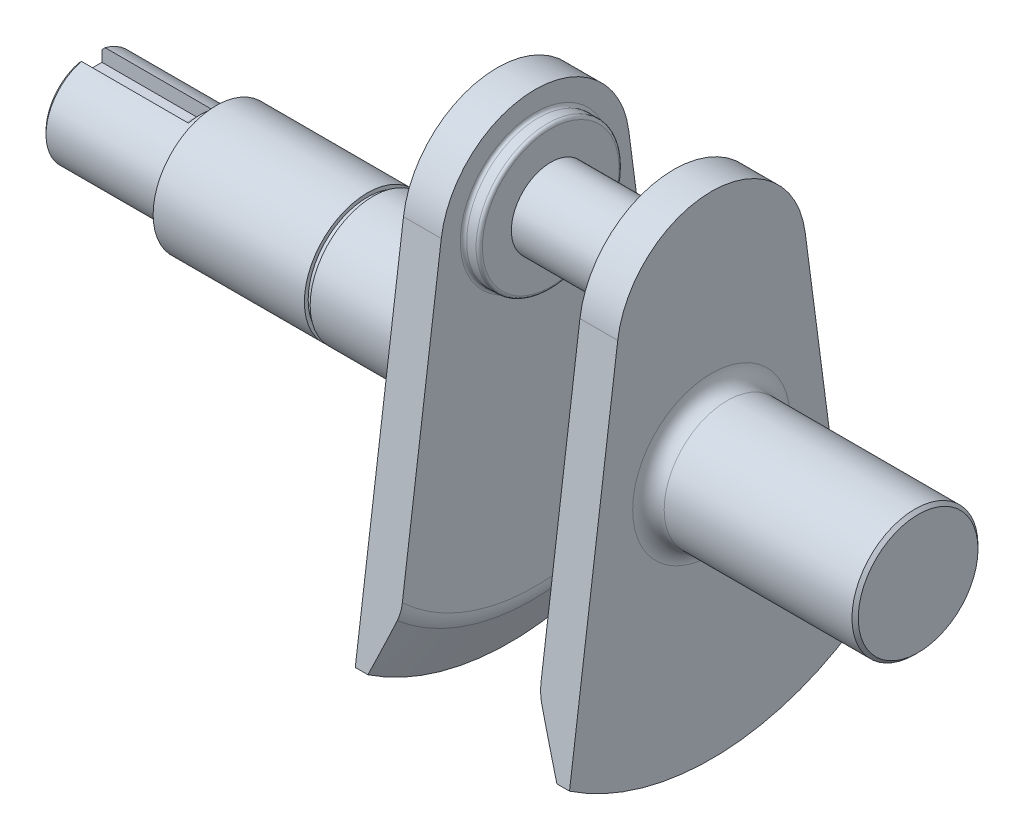
SolidWorks part; units mm, degrees
material "Alloy Steel"
ref_plane "Front Plane" through (0, 0, 0) normal (0, 0, 1) x (1, 0, 0)
ref_plane "Top Plane" through (0, 0, 0) normal (0, 1, 0) x (1, 0, 0)
ref_plane "Right Plane" through (0, 0, 0) normal (1, 0, 0) x (0, 0, -1)
sketch "Base Sketch" plane through (0, 0, 0) normal (1, 0, 0) x (0, 0, -1)
  circle A0 centre (0, 0) radius 12.7
  dimension "D1" = 25.4
extrude "Base" add sketch "Base Sketch" along normal blind 166.878
sketch "Front Sketch" plane through (0, 0, 0) normal (-1, 0, 0) x (0, 0, 1)
  circle A0 centre (0, 0) radius 9.525
  dimension "D1" = 19.05
extrude "Front Cut" cut sketch "Front Sketch" against normal blind 25.4 flip side to cut
sketch "Keyhole Sketch" plane through (0, 0, 0) normal (-1, 0, 0) x (0, 0, 1)
  line L1 (2.3876, 6.35) -> (-2.3876, 6.35)
  line L2 (2.3876, 6.35) -> (2.3876, 12.7)
  line L3 (2.3876, 12.7) -> (-2.3876, 12.7)
  line L4 (-2.3876, 6.35) -> (-2.3876, 12.7)
  line L5 (2.3876, 6.35) -> (-2.3876, 12.7) construction
  line L6 (2.3876, 12.7) -> (-2.3876, 6.35) construction
  circle A0 centre (0, 0) radius 9.525 construction
  circle A1 centre (0, 0) radius 9.525 construction
  point P0 (0, 9.525)
  dimension "D1" = 4.7752
  dimension "D2" = 3.175
extrude "Keyhole" cut sketch "Keyhole Sketch" against normal blind 22.225
fillet "Keyhole Fillet" radius 3.175 1 edges at (22.225, 6.35, 0)
sketch "Groove Sketch" plane through (0, 0, 0) normal (0, 0, 1) x (1, 0, 0)
  line L0 (166.878, 12.7) -> (25.4, 12.7) construction
  line L1 (57.0484, 11.938) -> (55.88, 11.938)
  line L2 (57.0484, 11.938) -> (57.0484, 13.462)
  line L3 (57.0484, 13.462) -> (55.88, 13.462)
  line L4 (55.88, 11.938) -> (55.88, 13.462)
  line L5 (57.0484, 11.938) -> (55.88, 13.462) construction
  line L6 (57.0484, 13.462) -> (55.88, 11.938) construction
  line L7 (0, 0) -> (166.878, 0) construction
  line L8 (166.878, -12.7) -> (166.878, 12.7) construction
  point P0 (56.4642, 12.7)
  dimension "D1" = 1.1684
  dimension "D2" = 1.524
  dimension "D3" = 55.88
revolve "Front Groove" cut sketch "Groove Sketch" angle 360 about L7
sketch "Exterior Sketch" plane through (0, 0, 0) normal (-1, 0, 0) x (0, 0, 1)
  circle A0 centre (0, 0) radius 12.7
  dimension "D1" = 25.4
extrude "Exterior Cut" cut sketch "Exterior Sketch" against normal blind 43.18 from offset 82.042 offset against normal yes
ref_plane "Center Plane" through (82.042, 0, 0) normal (1, 0, 0) x (0, 0, -1)
sketch "Shaft Sketch" plane through (82.042, 0, 0) normal (1, 0, 0) x (0, 0, -1)
  line L0 (0, 0) -> (0, 28.575) construction
  line L1 (-18.887, 31.0615) -> (-28.6055, -42.7577)
  line L2 (0, 28.575) -> (0, -91.1225) construction
  line L3 (18.887, 31.0615) -> (28.6055, -42.7577)
  circle A0 centre (0, 28.575) radius 14.4145
  circle A1 centre (0, 28.575) radius 19.05
  arc A2 (-28.6055, -42.7577) -> (28.6055, -42.7577) centre (0, 0) ccw
  dimension "D2" = 28.829
  dimension "D5" = 57.211
  dimension "D1" = 28.575
  dimension "D4" = 15
  dimension "D3" = 4.6355
extrude "Shaft" add sketch "Shaft Sketch" along normal blind 7.62 contours L1 A2 L3 A1 | A0 | A1 A0
sketch "Large Circle Sketch" plane through (89.662, 0, 0) normal (1, 0, 0) x (0, 0, -1)
  circle A0 centre (0, 28.575) radius 14.4145
  dimension "D1" = 28.829
extrude "Large Circle" add sketch "Large Circle Sketch" along normal blind 3.175
sketch "Bridge Sketch" plane through (92.837, 0, 0) normal (1, 0, 0) x (0, 0, -1)
  circle A0 centre (0, 28.575) radius 7.9375
  dimension "D1" = 15.875
extrude "Bridge" add sketch "Bridge Sketch" along normal blind 21.59
chamfer "Shaft Chamfer" distance 5.08 angle 65 1 edges at (89.662, -51.4441, 0) first distance on face at (85.852, -47.1009, 0)
ref_plane "Middle Plane" through (103.632, 0, 0) normal (1, 0, 0) x (0, 0, -1)
mirror "Large Circle Mirror" about plane through (103.632, 0, 0) normal (1, 0, 0) of "Shaft", "Large Circle"
mirror "Shaft Mirror" about plane through (103.632, 0, 0) normal (1, 0, 0) of "Shaft"
chamfer "Rear Chamfer" distance 5.08 angle 65 1 edges at (117.602, -51.4441, 0) first distance on face at (121.412, -47.1009, 0)
sketch "Back Base Sketch" plane through (125.222, 0, 0) normal (1, 0, 0) x (0, 0, -1)
  circle A0 centre (0, 0) radius 12.7
  dimension "D1" = 25.4
extrude "Back Base" add sketch "Back Base Sketch" along normal blind 41.656
fillet "Circle Fillet" radius 0.635 4 edges at (92.837, 28.575, -14.4145) (114.427, 28.575, -14.4145) (117.602, 28.575, -14.4145) (89.662, 28.575, -14.4145)
fillet "Base Fillet" radius 3.175 2 edges at (125.222, 0, 12.7) (82.042, 0, 12.7)
fillet "Shaft Fillet" radius 6.35 2 edges at (117.602, -40.55, 0) (89.662, -40.55, 0)
chamfer "Base Chamfer" distance 0.635 angle 45 2 edges at (0, -9.525, 0) (166.878, 0, -12.7)
